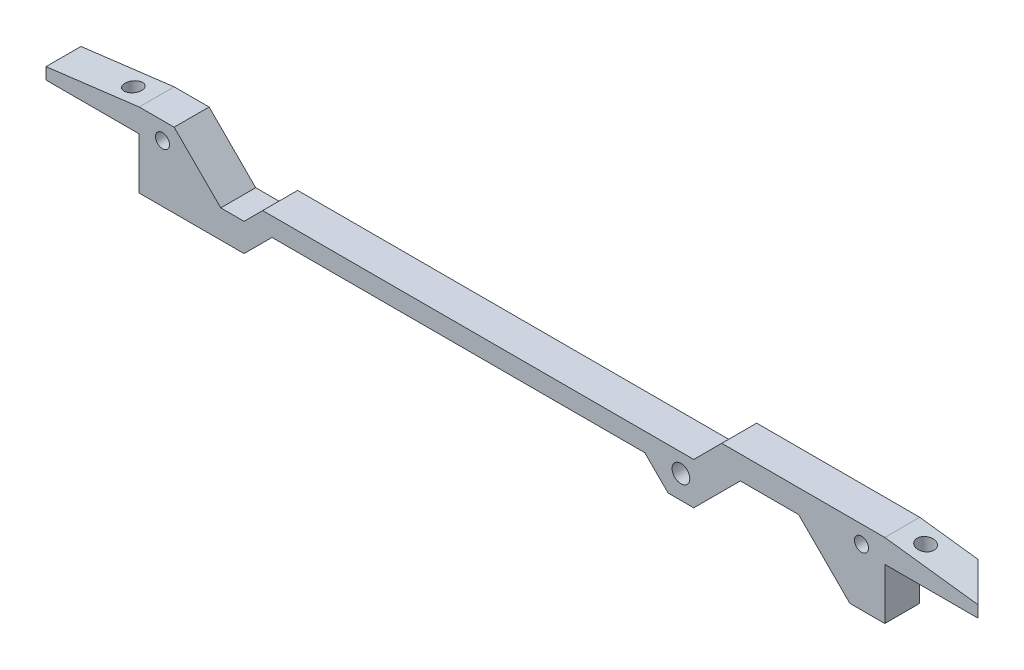
SolidWorks part; units mm, degrees
ref_plane "Front Plane" through (0, 0, 0) normal (0, 0, 1) x (1, 0, 0)
ref_plane "Top Plane" through (0, 0, 0) normal (0, 1, 0) x (1, 0, 0)
ref_plane "Right Plane" through (0, 0, 0) normal (1, 0, 0) x (0, 0, -1)
sketch "Sketch1" plane through (0, 0, 0) normal (0, 0, 1) x (1, 0, 0)
  line L0 (0, 12.7) -> (25.4, 12.7)
  line L5 (25.4, 12.7) -> (25.4, -1.27)
  line L6 (25.4, -1.27) -> (53.975, -1.27)
  line L7 (228.6, -1.27) -> (228.6, 12.7)
  line L10 (53.975, -1.27) -> (61.595, 6.35)
  line L12 (228.6, 19.05) -> (184.15, 19.05)
  line L13 (25.4, 19.05) -> (0, 15.875)
  line L14 (0, 15.875) -> (0, 12.7)
  line L15 (61.595, 6.35) -> (163.195, 6.35)
  line L18 (184.15, 19.05) -> (176.53, 11.43)
  line L19 (176.53, 11.43) -> (59.055, 11.43)
  line L20 (47.625, 6.35) -> (34.925, 19.05)
  line L21 (176.53, 0) -> (189.23, 12.7)
  line L22 (189.23, 12.7) -> (205.105, 12.7)
  line L23 (205.105, 12.7) -> (219.075, -1.27)
  line L24 (219.075, -1.27) -> (228.6, -1.27)
  line L25 (169.545, 0) -> (176.53, 0)
  line L26 (34.925, 19.05) -> (25.4, 19.05)
  line L28 (169.545, 0) -> (163.195, 6.35)
  line L29 (228.6, 19.05) -> (254, 15.875)
  line L30 (254, 15.875) -> (254, 12.7)
  line L31 (254, 12.7) -> (228.6, 12.7)
  line L33 (53.975, 6.35) -> (47.625, 6.35)
  line L34 (59.055, 11.43) -> (53.975, 6.35)
  point P20 (50.8, 6.35)
  point P29 (173.0375, 0)
  dimension "D1" = 12.7
  dimension "D2" = 25.4
  dimension "D3" = 228.6
  dimension "D4" = 6.35
  dimension "D5" = 28.575
  dimension "D6" = 12.7
  dimension "D7" = 15.875
  dimension "D8" = 12.7
  dimension "D9" = 1.27
  dimension "D10" = 3.175
  dimension "D11" = 9.525
  dimension "D12" = 9.525
  dimension "D13" = 6.35
  dimension "D14" = 44.45
  dimension "D15" = 25.4
  dimension "D16" = 13.97
  dimension "D17" = 3.175
  dimension "D18" = 45
  dimension "D19" = 6.35
  dimension "D20" = 25.4
  dimension "D21" = 55.5625
  dimension "D22" = 1.27
extrude "Boss-Extrude1" add sketch "Sketch1" against normal blind 9.525
sketch "Sketch2" plane through (0, 0, 0) normal (0, 0, 1) x (1, 0, 0)
  line L0 (228.6, 19.05) -> (184.15, 19.05) construction
  line L1 (25.4, 12.7) -> (25.4, -1.27) construction
  line L2 (228.6, -1.27) -> (228.6, 12.7) construction
  circle A0 centre (31.75, 14.2875) radius 1.905
  circle A1 centre (95.25, 14.2875) radius 1.905
  circle A2 centre (158.75, 14.2875) radius 1.905
  circle A3 centre (222.25, 14.2875) radius 1.905
  circle A6 centre (173.0375, 6.35) radius 2.413
  circle A7 centre (173.0375, 6.35) radius 2.413
  dimension "D1" = 3.81
  dimension "D2" = 4.7625
  dimension "D3" = 6.35
  dimension "D5" = 6.35
  dimension "D6" = 0.381
  dimension "D4" = 4
extrude "Cut-Extrude2" cut sketch "Sketch2" against normal through all
chamfer "Chamfer1" distance 9.525 angle 45 1 edges at (254, 14.2875, -9.525)
sketch "Sketch4" plane through (0, 12.7, 0) normal (0, -1, 0) x (-1, 0, 0)
  line L1 (-228.6, 9.525) -> (-228.6, 0) construction
  line L2 (-25.4, 9.525) -> (-25.4, 0) construction
  circle A0 centre (-234.95, 4.7652) radius 2.286
  circle A1 centre (-19.05, 4.7652) radius 2.286
  dimension "D2" = 4.572
  dimension "D1" = 6.35
  dimension "D3" = 6.35
extrude "Cut-Extrude4" cut sketch "Sketch4" against normal up to next
